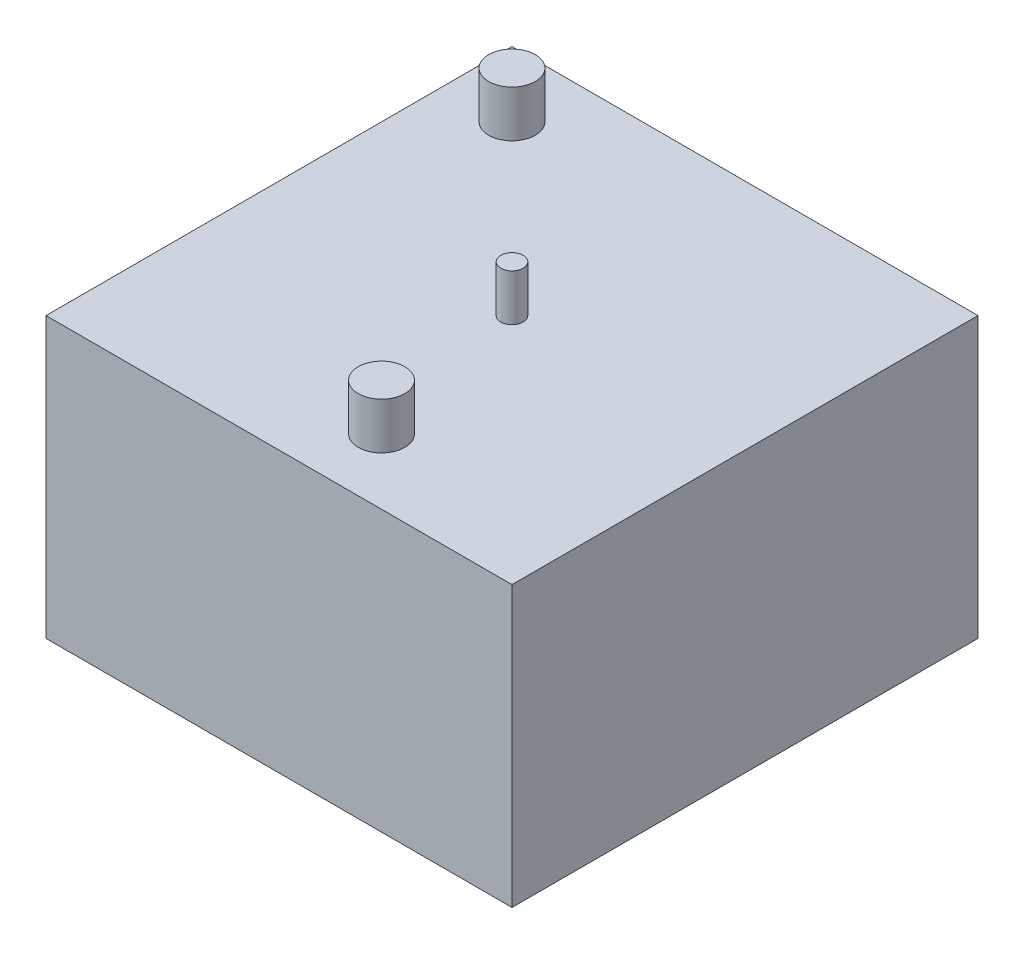
SolidWorks part; units mm, degrees
ref_plane "Front Plane" through (0, 0, 0) normal (0, 0, 1) x (1, 0, 0)
ref_plane "Top Plane" through (0, 0, 0) normal (0, 1, 0) x (1, 0, 0)
ref_plane "Right Plane" through (0, 0, 0) normal (1, 0, 0) x (0, 0, -1)
sketch "Sketch1" plane through (0, 0, 0) normal (0, 1, 0) x (1, 0, 0)
  line L1 (0, 0) -> (63.5, 0)
  line L2 (0, 0) -> (0, 63.5)
  line L3 (0, 63.5) -> (63.5, 63.5)
  line L4 (63.5, 0) -> (63.5, 63.5)
  dimension "D1" = 63.5
  dimension "D2" = 63.5
extrude "Boss-Extrude1" add sketch "Sketch1" along normal blind 38.1
sketch "Sketch2" plane through (0, 38.1, 0) normal (0, 1, 0) x (1, 0, 0)
  line L0 (0, 63.5) -> (63.5, 0) construction
  line L1 (0, 0) -> (63.5, 0) construction
  line L4 (63.5, 63.5) -> (0, 0) construction
  line L11 (63.5, 0) -> (63.5, 63.5) construction
  line L16 (63.5, 63.5) -> (0, 63.5) construction
  circle A0 centre (31.75, 31.75) radius 1.524
  circle A1 centre (8.89, 54.61) radius 3.175
  circle A2 centre (36.83, 8.89) radius 3.175
  point P15 (0, 0)
  dimension "D1" = 3.048
  dimension "D2" = 6.35
  dimension "D3" = 6.35
  dimension "D4" = 8.89
  dimension "D5" = 26.67
  dimension "D6" = 8.89
extrude "Boss-Extrude2" add sketch "Sketch2" along normal blind 6.35
